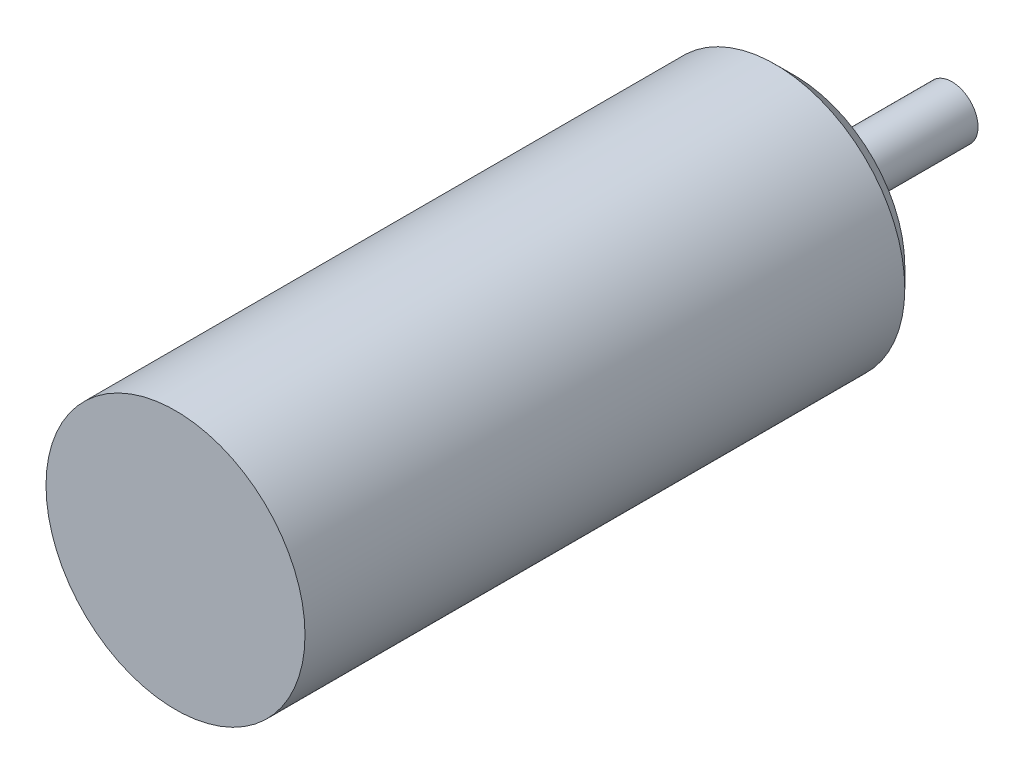
SolidWorks part; units mm, degrees
ref_plane "Front Plane" through (0, 0, 0) normal (0, 0, 1) x (1, 0, 0)
ref_plane "Top Plane" through (0, 0, 0) normal (0, 1, 0) x (1, 0, 0)
ref_plane "Right Plane" through (0, 0, 0) normal (1, 0, 0) x (0, 0, -1)
sketch "Sketch1" plane through (0, 0, 0) normal (0, 0, 1) x (1, 0, 0)
  circle A0 centre (0, 0) radius 19.8
  dimension "D1" = 39.6
extrude "Boss-Extrude1" add sketch "Sketch1" along normal blind 94.7
sketch "face mounting holes" plane through (0, 0, 0) normal (0, 0, -1) x (-1, 0, 0)
  point P0 (0, 12.5)
  point P1 (0, 0)
  point P2 (0, 0)
  point P4 (12.5, 0)
  point P5 (0, -12.5)
  point P6 (-12.5, 0)
  point P7 (0, 0)
  dimension "D2" = 25
  dimension "D1" = 4
hole_wizard "M4x0.7 Tapped Hole1" positions "Sketch3" profile "Sketch5" tap size "M4x0.7" standard "ANSI Metric"
sketch "Sketch3" plane through (0, 0, 0) normal (0, 0, -1) x (-1, 0, 0)
  point P0 (0, 12.5)
  point P3 (-12.5, 0)
  point P6 (0, -12.5)
  point P9 (12.5, 0)
sketch "Sketch5" plane through (0, 12.5, 0) normal (1, 0, 0) x (0, 1, 0)
  line L0 (0, 0) -> (0, 4.9914)
  line L1 (0, 4.9914) -> (1.65, 4)
  line L2 (1.65, 4) -> (1.65, 0.375)
  line L3 (1.65, 0.375) -> (2.025, 0)
  line L5 (2.025, 0) -> (0, 0)
  line L6 (-1.65, 0.375) -> (-2.025, 0) construction
  line L10 (0, 4.9914) -> (-1.65, 4) construction
  line L11 (0, -6.35) -> (0, 107.95) construction
  dimension "Tap Drill Dia." = 3.3
  dimension "Tap Drill Depth" = 4
  dimension "Near C'Sink Dia." = 4.05
  dimension "Near C'Sink Angle" = 90
  dimension "Drill Angle" = 118
cosmetic thread "Hole Thread1"
cosmetic thread "Hole Thread2"
cosmetic thread "Hole Thread3"
cosmetic thread "Hole Thread4"
sketch "Sketch6" plane through (0, 0, 0) normal (0, 0, -1) x (-1, 0, 0)
  circle A0 centre (0, 0) radius 4
  dimension "D1" = 8
extrude "Boss-Extrude2" add sketch "Sketch6" along normal blind 24
chamfer "Chamfer1" distance 3 angle 45 1 edges at (19.8, 0, 0)
